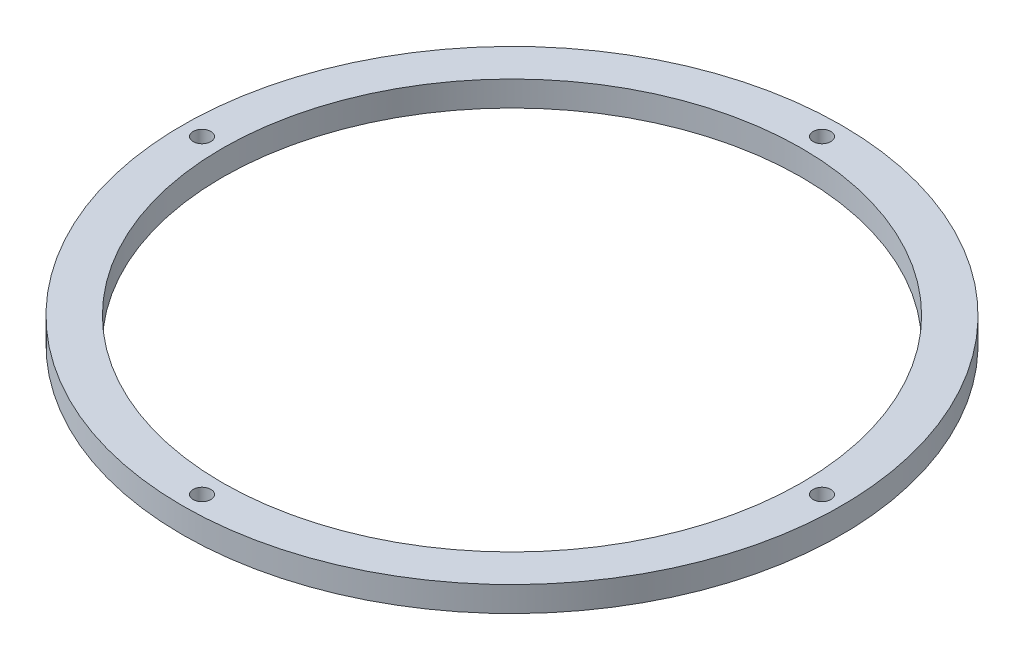
SolidWorks part; units mm, degrees
ref_plane "Front Plane" through (0, 0, 0) normal (0, 0, 1) x (1, 0, 0)
ref_plane "Top Plane" through (0, 0, 0) normal (0, 1, 0) x (1, 0, 0)
ref_plane "Right Plane" through (0, 0, 0) normal (1, 0, 0) x (0, 0, -1)
sketch "Sketch1" plane through (0, 0, 0) normal (0, 1, 0) x (1, 0, 0)
  circle A0 centre (0, 0) radius 111.5
  circle A1 centre (0, 0) radius 98
  dimension "D1" = 223
  dimension "D2" = 196
extrude "Boss-Extrude1" add sketch "Sketch1" along normal blind 8.5
sketch "Sketch2" plane through (0, 8.5, 0) normal (0, 1, 0) x (1, 0, 0)
  circle A0 centre (0, 0) radius 104.875 construction
  circle A1 centre (0, 104.875) radius 3
  circle A2 centre (-104.875, 0) radius 3
  circle A3 centre (104.875, 0) radius 3
  circle A4 centre (0, -104.875) radius 3
  point P11 (0, 0)
  point P12 (0, 0)
  point P13 (0, 0)
  dimension "D1" = 209.75
  dimension "D2" = 6
  dimension "D3" = 6
  dimension "D4" = 6
  dimension "D5" = 6
extrude "Cut-Extrude1" cut sketch "Sketch2" against normal through all contours A1 | A3 | A4 | A2
